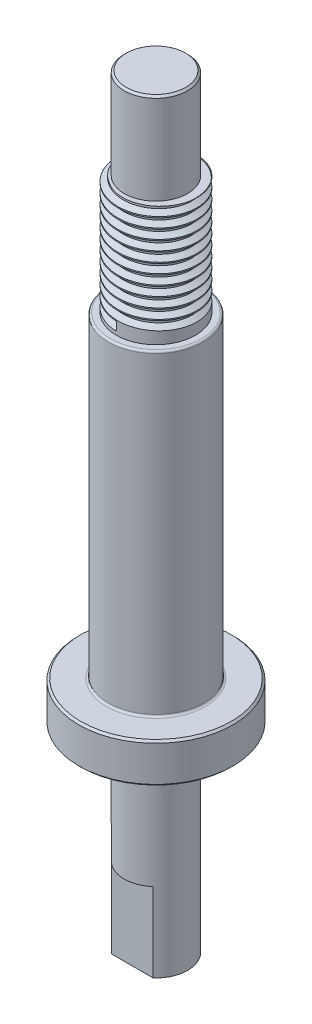
SolidWorks part; units mm, degrees
material "6061 Alloy"
ref_plane "Front Plane" through (0, 0, 0) normal (0, 0, 1) x (1, 0, 0)
ref_plane "Top Plane" through (0, 0, 0) normal (0, 1, 0) x (1, 0, 0)
ref_plane "Right Plane" through (0, 0, 0) normal (1, 0, 0) x (0, 0, -1)
sketch "Sketch1" plane through (0, 0, 0) normal (0, 1, 0) x (1, 0, 0)
  circle A0 centre (0, 0) radius 9.75
  dimension "D1" = 19.5
extrude "Boss-Extrude1" add sketch "Sketch1" along normal blind 5
sketch "Sketch2" plane through (0, 5, 0) normal (0, 1, 0) x (1, 0, 0)
  circle A0 centre (0, 0) radius 6
  dimension "D1" = 12
extrude "Boss-Extrude2" add sketch "Sketch2" along normal blind 40
sketch "Sketch3" plane through (0, 45, 0) normal (0, 1, 0) x (1, 0, 0)
  circle A0 centre (0, 0) radius 4
  dimension "D1" = 8
extrude "Boss-Extrude3" add sketch "Sketch3" along normal blind 26.5
sketch "Sketch4" plane through (0, 0, 0) normal (0, -1, 0) x (1, 0, 0)
  circle A0 centre (0, 0) radius 4
  dimension "D1" = 8
extrude "Boss-Extrude4" add sketch "Sketch4" along normal blind 25
sketch "Sketch5" plane through (0, -25, 0) normal (0, -1, 0) x (1, 0, 0)
  line L0 (-2.6458, 3) -> (2.6458, 3)
  arc A0 (2.6458, 3) -> (-2.6458, 3) centre (0, 0) ccw
  dimension "D2" = 8
  dimension "D1" = 3
extrude "Cut-Extrude1" cut sketch "Sketch5" against normal blind 10
sketch "Sketch10" plane through (0, 45, 0) normal (0, 1, 0) x (1, 0, 0)
  circle A0 centre (0, 0) radius 4
  circle A1 centre (0, 0) radius 5
  dimension "D1" = 10
  dimension "D2" = 8
extrude "Boss-Extrude5" add sketch "Sketch10" along normal blind 15
ref_plane "Plane1" through (0, 46, 0) normal (0, 1, 0) x (1, 0, 0)
sketch "Sketch11" plane through (0, 46, 0) normal (0, 1, 0) x (1, 0, 0)
  circle A0 centre (0, 0) radius 5
curve "Helix/Spiral1" pitch 1.25 height 15.3125 turns 12.25
ref_plane "Plane3" through (-5, 61.3125, 0) normal (0, 0.0398, -0.9992) x (-1, 0, 0)
sketch "Sketch14" plane through (-5, 61.3125, 0) normal (0, 0.0398, -0.9992) x (-1, 0, 0)
  line L0 (0.0126, 0.5419) -> (0.0126, -0.5748)
  line L1 (0.0126, -0.5748) -> (-0.6774, -0.1764)
  line L2 (-0.6774, 0.1436) -> (0.0126, 0.5419)
  line L3 (-0.6774, 0.1436) -> (-0.6774, -0.1764)
  point P2 (0.0126, -0.0164)
  dimension "D1" = 60
  dimension "D2" = 60
  dimension "D3" = 0.32
  dimension "D4" = 0.69
sweep "Cut-Sweep1" cut profiles "Sketch14" path "Helix/Spiral1"
sketch "Sketch16" plane through (0, 45, 0) normal (0, 1, 0) x (1, 0, 0)
  line L0 (0, -3) -> (0, 6) construction
  line L1 (-2.6458, -3) -> (2.6458, -3) construction
  circle A0 centre (0, 0) radius 6 construction
ref_plane "Plane5" through (0, 45, -6) normal (0, 0, -1) x (-1, 0, 0)
sketch "Sketch17" plane through (0, 45, -6) normal (0, 0, -1) x (-1, 0, 0)
  line L0 (0, -2.8) -> (0, -38) construction
  line L1 (1, -2.8) -> (1, -38)
  line L2 (-1, -2.8) -> (-1, -38)
  line L3 (9.75, -40) -> (-9.75, -40) construction
  arc A0 (1, -2.8) -> (-1, -2.8) centre (0, -2.8) ccw
  arc A1 (-1, -38) -> (1, -38) centre (0, -38) ccw
  point P3 (0, -20.4)
  dimension "D3" = 2
  dimension "D1" = 35.2
  dimension "D2" = 2
fillet "Fillet2" radius 0.25 2 edges at (0, 5, 6) (0, 45, 6)
extrude "Cut-Extrude2" cut sketch "Sketch17" against normal blind 1
chamfer "Chamfer1" distance 0.25 angle 45 1 edges at (0, 71.5, 4)
chamfer "Chamfer2" distance 0.25 angle 45 3 edges at (0, 5, 9.75) (0, 0, 4) (0, 0, 9.75)
